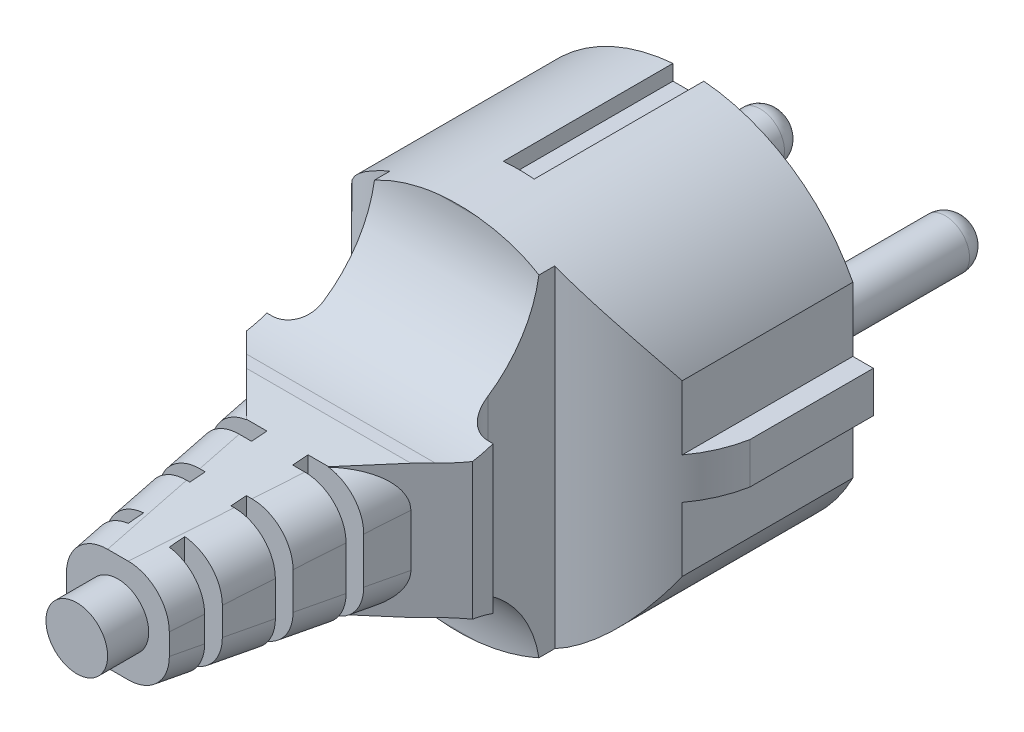
SolidWorks part; units mm, degrees
ref_plane "Front Plane" through (0, 0, 0) normal (0, 0, 1) x (1, 0, 0)
ref_plane "Top Plane" through (0, 0, 0) normal (0, 1, 0) x (1, 0, 0)
ref_plane "Right Plane" through (0, 0, 0) normal (1, 0, 0) x (0, 0, -1)
sketch "Sketch1" plane through (0, 0, 0) normal (0, 0, 1) x (1, 0, 0)
  line L0 (0, 0) -> (0, 19.6128) construction
  line L2 (-16, 2) -> (-16, 8.2462)
  line L3 (16, -2) -> (16, -8.2462)
  line L4 (18, -2) -> (16, -2)
  line L7 (-18, -2) -> (-18, 2)
  line L8 (-18, -2) -> (-16, -2)
  line L9 (-18, 2) -> (-16, 2)
  line L10 (-16, -2) -> (-16, -8.2462)
  line L11 (18, -2) -> (18, 2)
  line L12 (18, 2) -> (16, 2)
  line L13 (16, 2) -> (16, 8.2462)
  line L14 (0, 0) -> (-8.7268, 0) construction
  arc A0 (-16, 8.2462) -> (16, 8.2462) centre (0, 0) cw
  arc A1 (-16, -8.2462) -> (16, -8.2462) centre (0, 0) ccw
  point P11 (-18, 0)
  point P16 (0, 16)
extrude "Boss-Extrude1" add sketch "Sketch1" along normal blind 55.5
sketch "Sketch4" plane through (0, 0, 0) normal (0, 1, 0) x (1, 0, 0)
  line L0 (-18, 0) -> (-18, -12)
  line L1 (-18, -55.5) -> (-18, 0) construction
  line L2 (-8, -27.5) -> (-8, -21)
  line L3 (5, -55.5) -> (-5, -55.5)
  line L4 (-16, -55.5) -> (16, -55.5) construction
  line L6 (-18, 0) -> (18, 0)
  line L7 (-11, -30) -> (-10.5, -30)
  line L8 (-11, -30) -> (-11, -32)
  line L9 (-5, -55.5) -> (-8, -35)
  line L10 (0, -55.5) -> (0, -36.3973) construction
  line L11 (-11, -32) -> (-8, -35)
  line L12 (5, -55.5) -> (8, -35)
  line L18 (11, -32) -> (8, -35)
  line L19 (11, -30) -> (11, -32)
  line L20 (11, -30) -> (10.5, -30)
  line L21 (8, -27.5) -> (8, -21)
  line L22 (18, 0) -> (18, -12)
  arc A0 (-10.5, -30) -> (-8, -27.5) centre (-10.5, -27.5) ccw
  arc A1 (-8, -21) -> (-18, -12) centre (-7.1777, -10.0308) cw
  arc A2 (8, -21) -> (18, -12) centre (7.1777, -10.0308) ccw
  arc A3 (10.5, -30) -> (8, -27.5) centre (10.5, -27.5) cw
  point P11 (-8, -30)
  point P41 (0, 0)
  dimension "D2" = 2.5
extrude "Cut-Extrude3" cut sketch "Sketch4" against normal mid plane 40 flip side to cut
sketch "Sketch5" plane through (0, 0, 0) normal (0, 0, -1) x (-1, 0, 0)
  line L1 (0, 19.68) -> (1.5, 19.68)
  line L2 (1.5, 19.68) -> (1.5, 17.9374)
  line L3 (1.5, 17.9374) -> (1.5, 16.4374)
  line L4 (1.5, 16.4374) -> (-1.5, 16.4374)
  line L5 (-1.5, 16.4374) -> (-1.5, 19.68)
  line L6 (-1.5, 19.68) -> (0, 19.68)
  arc A0 (16, 8.2462) -> (-16, 8.2462) centre (0, 0) ccw construction
extrude "Cut-Extrude4" cut sketch "Sketch5" against normal blind 16.5
mirror "Mirror1" about plane through (0, 0, 0) normal (0, 1, 0) of "Cut-Extrude4"
sketch "Sketch6" plane through (0, 0, 0) normal (0, 0, 1) x (1, 0, 0)
  circle A0 centre (0, 0) radius 5
extrude "Boss-Extrude3" add sketch "Sketch6" along normal blind 55.5
sketch "Sketch7" plane through (0, 0, 0) normal (1, 0, 0) x (0, 0, -1)
  line L0 (-22.4, 17.9374) -> (-22.4, 20.91)
  line L1 (0, 0) -> (-58.6156, 0) construction
  line L2 (-55.5, -5) -> (-55.5, 5)
  line L3 (-22.4, 20.91) -> (0, 20.91)
  line L4 (-35, -16.1245) -> (-35, 16.1245) construction
  line L5 (-55.5, -17.2916) -> (-55.5, 17.2916) construction
  line L6 (-55.5, 5) -> (-35, 6.5)
  line L7 (-35, 6.5) -> (-33.8, 6.5)
  line L8 (-22.4, 17.9) -> (-22.4, 17.9374)
  line L9 (0, 17.9374) -> (0, -17.9374)
  line L10 (0, 20.91) -> (0, 17.9374)
  line L11 (-35, -6.5) -> (-33.8, -6.5)
  line L12 (-55.5, -5) -> (-35, -6.5)
  line L13 (-22.4, -17.9) -> (-22.4, -20.334)
  line L14 (-22.4, -20.334) -> (0, -20.334)
  line L15 (0, -20.334) -> (0, -17.9374)
  arc A0 (-33.8, 6.5) -> (-22.4, 17.9) centre (-33.8, 17.9) ccw
  arc A1 (-33.8, -6.5) -> (-22.4, -17.9) centre (-33.8, -17.9) cw
  point P21 (0, 0)
  point P27 (-55.5, 0)
  dimension "D1" = 11.4
extrude "Cut-Extrude6" cut sketch "Sketch7" against normal mid plane 55.5 flip side to cut contours L3 L10 L9 L15 L14 L13 A1 L11 L12 L2 L6 L7 A0 L8 L0
fillet "Fillet3" radius 4 4 edges at (6.5, -5.75, 45.25) (-6.5, -5.75, 45.25) (-6.5, 5.75, 45.25) (6.5, 5.75, 45.25)
sketch "Sketch8" plane through (0, 0, 0) normal (0, 0, -1) x (-1, 0, 0)
  circle A0 centre (-9, 0) radius 2.35
extrude "Boss-Extrude4" add sketch "Sketch8" along normal blind 18
fillet "Fillet4" radius 2 1 edges at (6.65, 0, -18)
mirror "Mirror2" about plane through (0, 0, 0) normal (1, 0, 0) of "Fillet4", "Boss-Extrude4"
sketch "Sketch10" plane through (0, 0, 0) normal (0, 1, 0) x (1, 0, 0)
  line L2 (2.0001, -39) -> (10.4648, -39)
  line L3 (10.4648, -46.5) -> (2.0001, -46.5)
  line L4 (10.4648, -39) -> (10.4648, -40.5)
  line L5 (10.4648, -40.5) -> (2.0001, -40.5)
  line L7 (2.0001, -40.5) -> (2.0001, -39)
  line L9 (2.0001, -45) -> (10.4648, -45)
  line L10 (10.4648, -45) -> (10.4648, -46.5)
  line L11 (2.0001, -46.5) -> (2.0001, -45)
  line L12 (10.4648, -52.5) -> (2.0001, -52.5)
  line L13 (2.0001, -51) -> (10.4648, -51)
  line L14 (10.4648, -51) -> (10.4648, -52.5)
  line L15 (2.0001, -52.5) -> (2.0001, -51)
  line L20 (-2.0001, -52.5) -> (-2.0001, -51)
  line L21 (-10.4648, -51) -> (-10.4648, -52.5)
  line L22 (-2.0001, -51) -> (-10.4648, -51)
  line L23 (-10.4648, -52.5) -> (-2.0001, -52.5)
  line L24 (-2.0001, -46.5) -> (-2.0001, -45)
  line L25 (-10.4648, -45) -> (-10.4648, -46.5)
  line L26 (-2.0001, -45) -> (-10.4648, -45)
  line L27 (-2.0001, -40.5) -> (-2.0001, -39)
  line L28 (-10.4648, -40.5) -> (-2.0001, -40.5)
  line L29 (-10.4648, -39) -> (-10.4648, -40.5)
  line L30 (-10.4648, -46.5) -> (-2.0001, -46.5)
  line L31 (-2.0001, -39) -> (-10.4648, -39)
  dimension "D1" = 3
extrude "Cut-Extrude8" cut sketch "Sketch10" against normal mid plane 24
sketch "Sketch11" plane through (0, 0, 0) normal (0, 0, 1) x (1, 0, 0)
  circle A0 centre (0, 0) radius 3
extrude "Boss-Extrude6" add sketch "Sketch11" along normal blind 59.5
sketch "Sketch12" plane through (0, 0, 0) normal (0, 0, -1) x (-1, 0, 0)
  circle A1 centre (0, -9) radius 2.35
extrude "Cut-Extrude9" cut sketch "Sketch12" against normal blind 10 contours A1
